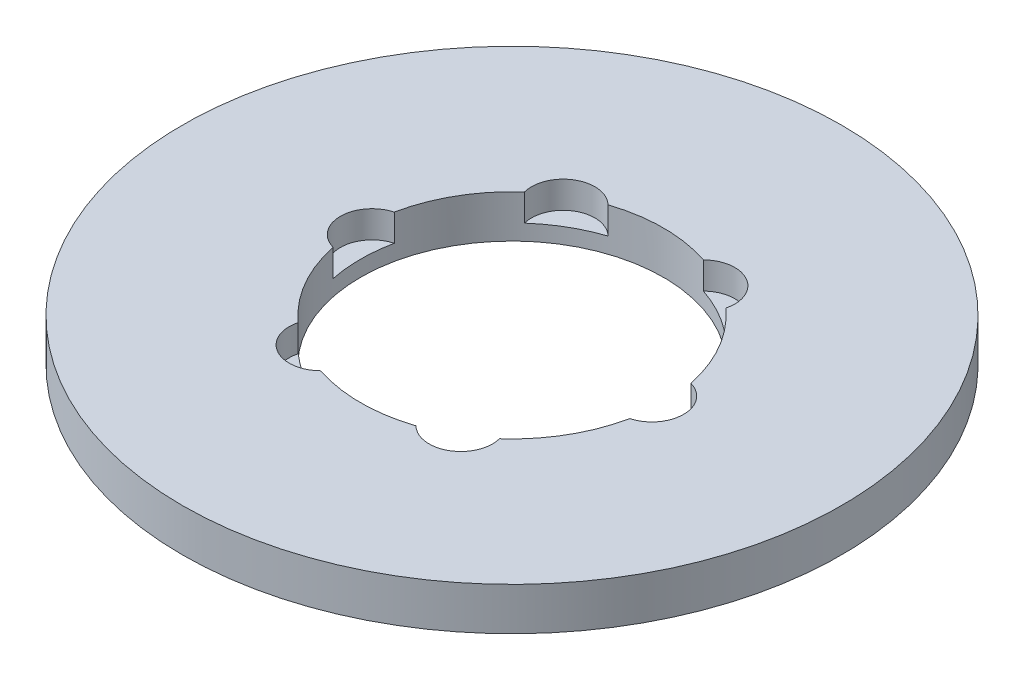
SolidWorks part; units mm, degrees
ref_plane "Front Plane" through (0, 0, 0) normal (0, 0, 1) x (1, 0, 0)
ref_plane "Top Plane" through (0, 0, 0) normal (0, 1, 0) x (1, 0, 0)
ref_plane "Right Plane" through (0, 0, 0) normal (1, 0, 0) x (0, 0, -1)
sketch "Sketch1" plane through (0, 0, 0) normal (0, 1, 0) x (1, 0, 0)
  circle A0 centre (0, 0) radius 92.5
  dimension "FLANGE_OD" = 185
extrude "Boss-Extrude1" add sketch "Sketch1" along normal blind 12
sketch "Sketch2" plane through (0, 0, 0) normal (0, 1, 0) x (1, 0, 0)
  circle A0 centre (0, 0) radius 42.5
  dimension "BORE_D" = 85
extrude "Cut-Extrude1" cut sketch "Sketch2" along normal through all
sketch "Sketch3" plane through (0, 12, 0) normal (0, 1, 0) x (1, 0, 0)
  circle A0 centre (0, 0) radius 39.2617 construction
  circle A1 centre (-39.2617, 0) radius 8.9
  dimension "BOLT_D" = 17.8
  dimension "BOLT_PCD" = 78.5235
extrude "Cut-Extrude2" cut sketch "Sketch3" against normal blind 7.5869
pattern_circular "CirPattern1" count 6 over 360 about axis through (0, 0, 0) along (0, 1, 0) of "Cut-Extrude2"
